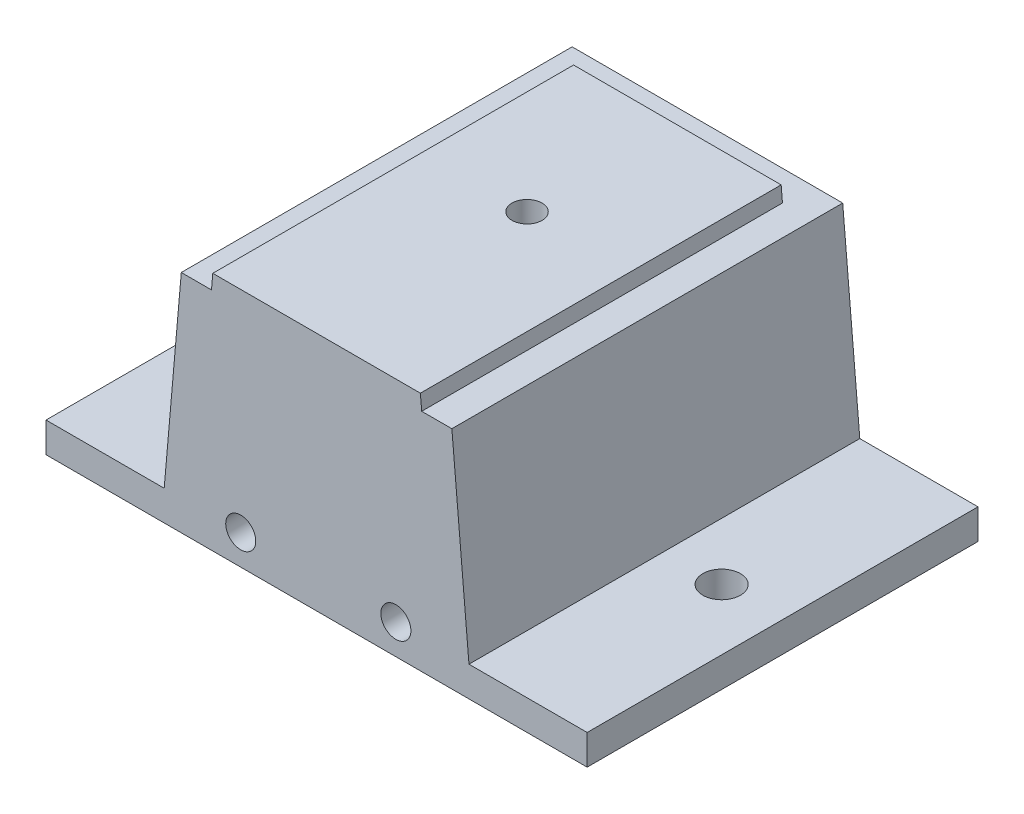
SolidWorks part; units mm, degrees
material "6061 Alloy"
ref_plane "Front Plane" through (0, 0, 0) normal (0, 0, 1) x (1, 0, 0)
ref_plane "Top Plane" through (0, 0, 0) normal (0, 1, 0) x (1, 0, 0)
ref_plane "Right Plane" through (0, 0, 0) normal (1, 0, 0) x (0, 0, -1)
sketch "Sketch1" plane through (0, 0, 0) normal (0, 0, 1) x (1, 0, 0)
  line L0 (0, 0) -> (0, 65.9076) construction
  line L1 (57.15, 0) -> (-57.15, 0)
  line L2 (-57.15, 0) -> (-57.15, 6.35)
  line L3 (-57.15, 6.35) -> (-32.1861, 6.35)
  line L4 (-32.1861, 6.35) -> (-28.575, 47.625)
  line L5 (-21.923, 50.8) -> (21.923, 50.8)
  line L6 (57.15, 0) -> (57.15, 6.35)
  line L7 (57.15, 6.35) -> (32.1861, 6.35)
  line L8 (32.1861, 6.35) -> (28.575, 47.625)
  line L9 (-28.575, 47.625) -> (-22.2007, 47.625)
  line L10 (-22.2007, 47.625) -> (-21.923, 50.8)
  line L11 (21.923, 50.8) -> (22.2007, 47.625)
  line L12 (22.2007, 47.625) -> (28.575, 47.625)
  point P12 (0, 50.8)
  point P15 (-22.0619, 49.2125)
  dimension "D3" = 50.8
  dimension "D4" = 95
  dimension "D6" = 3.175
extrude "Boss-Extrude1" add sketch "Sketch1" along normal mid plane 82.55
shell "Shell1" thickness 6.35 removed face at (0, 0, 0)
sketch "Sketch7" plane through (0, 0, 0) normal (1, 0, 0) x (0, 0, -1)
  line L0 (41.275, 47.625) -> (34.925, 47.625)
  line L2 (-41.275, 47.625) -> (41.275, 47.625) construction
  line L3 (34.925, 47.625) -> (34.925, 50.8)
  line L4 (-41.275, 50.8) -> (41.275, 50.8) construction
  line L5 (34.925, 50.8) -> (41.275, 50.8)
  line L6 (41.275, 50.8) -> (41.275, 47.625)
  dimension "D1" = 6.35
extrude "Cut-Extrude2" cut sketch "Sketch7" against normal through all both and the other way through all
sketch "Sketch8" plane through (0, 0, -50.8) normal (0, 1, 0) x (1, 0, 0)
  line L4 (0, -78.74) -> (0, -22.86) construction
  circle A1 centre (44.2781, -50.8) radius 3.9687
  circle A2 centre (-44.2781, -50.8) radius 3.9687
  dimension "D5" = 7.9375
extrude "Cut-Extrude3" cut sketch "Sketch8" along normal through all
hole_wizard "1/4 (0.25) Diameter Hole1" positions "Sketch9" profile "Sketch10" hole size "1/4" standard "ANSI Inch" end condition up to next
sketch "Sketch9" plane through (0, 50.8, 0) normal (0, 1, 0) x (1, 0, 0)
  line L0 (0, 0) -> (0, 25.0279) construction
  point P0 (0, 3.175)
sketch "Sketch10" plane through (0, 50.8, -3.175) normal (1, 0, 0) x (0, 0, 1)
  line L0 (0, 0) -> (0, 6.35)
  line L1 (0, 6.35) -> (3.175, 6.35)
  line L2 (3.175, 6.35) -> (3.175, 0)
  line L5 (3.175, 0) -> (0, 0)
  line L11 (0, -6.35) -> (0, 107.95) construction
  dimension "Thru Hole Dia." = 6.35
  dimension "Thru Hole Depth" = 6.35
hole_wizard "1/4 (0.25) Diameter Hole2" positions "Sketch11" profile "Sketch12" hole size "1/4" standard "ANSI Inch" end condition through all
sketch "Sketch11" plane through (0, 0, -41.275) normal (0, 0, -1) x (-1, 0, 0)
  point P0 (-16.7468, 6.35)
  point P3 (16.0172, 6.35)
  point P6 (-21.1452, 6.35)
  point P7 (16.0172, 6.35)
  point P9 (0, 0)
  point P10 (-16.7468, 6.35)
sketch "Sketch12" plane through (16.7468, 6.35, -41.275) normal (1, 0, 0) x (0, 1, 0)
  line L0 (0, 0) -> (0, 82.55)
  line L1 (0, 82.55) -> (3.175, 82.55)
  line L2 (3.175, 82.55) -> (3.175, 0)
  line L5 (3.175, 0) -> (0, 0)
  line L11 (0, -6.35) -> (0, 107.95) construction
  dimension "Thru Hole Dia." = 6.35
  dimension "Thru Hole Depth" = 82.55
equation "\"BedBaseDraftAngle\"=95"
equation "\"D4@Sketch1\"=\"BedBaseDraftAngle\""
